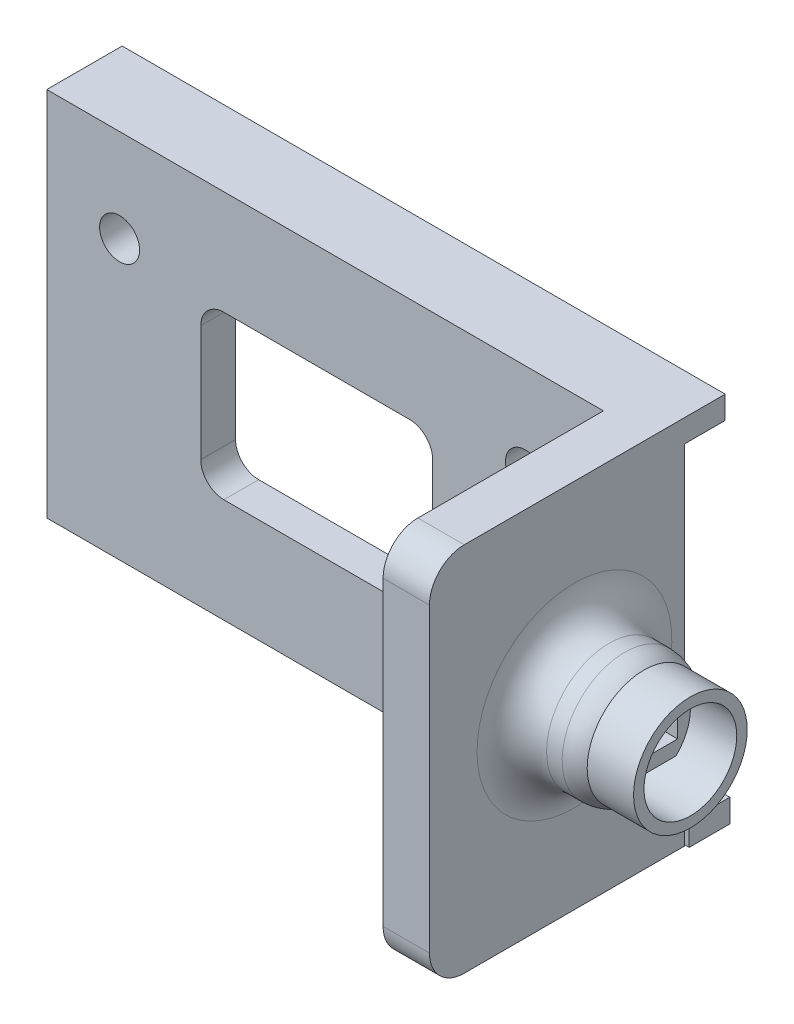
SolidWorks part; units mm, degrees
ref_plane "Front Plane" through (0, 0, 0) normal (0, 0, 1) x (1, 0, 0)
ref_plane "Top Plane" through (0, 0, 0) normal (0, 1, 0) x (1, 0, 0)
ref_plane "Right Plane" through (0, 0, 0) normal (1, 0, 0) x (0, 0, -1)
sketch "Sketch1" plane through (0, 0, 0) normal (0, 0, 1) x (1, 0, 0)
  line L1 (0, 0) -> (52, 0)
  line L2 (0, 0) -> (0, -32)
  line L3 (0, -32) -> (52, -32)
  line L4 (52, 0) -> (52, -32)
  dimension "D1" = 52
  dimension "D2" = 32
extrude "Boss-Extrude1" add sketch "Sketch1" along normal blind 3
ref_plane "Plane1" through (0, 0, 2) normal (0, 0, -1) x (-1, 0, 0)
sketch "Sketch2" plane through (0, 0, 2) normal (0, 0, -1) x (-1, 0, 0)
  line L1 (-48, 0) -> (-52, 0)
  line L2 (-48, 0) -> (-48, -32)
  line L3 (-48, -32) -> (-52, -32)
  line L4 (-52, 0) -> (-52, -32)
  dimension "D1" = 4
extrude "Boss-Extrude2" add sketch "Sketch2" against normal blind 20
fillet "Fillet1" radius 3 2 edges at (50, -32, 22) (50, 0, 22)
sketch "Sketch4" plane through (0, 0, 3) normal (0, 0, 1) x (1, 0, 0)
  line L0 (48, 0) -> (0, 0) construction
  circle A0 centre (41.2777, -8) radius 1.725
  circle A1 centre (6.2777, -8) radius 1.725
  dimension "D1" = 35
  dimension "D2" = 8
  dimension "D3" = 8
extrude "Cut-Extrude2" cut sketch "Sketch4" against normal up to surface (3 mm away) up to face at (26, -16, 0)
sketch "Sketch5" plane through (0, 0, 0) normal (0, 0, -1) x (-1, 0, 0)
  line L6 (0, 0) -> (0, -32) construction
  line L7 (-52.3955, -31.9041) -> (0, -31.9041)
  line L8 (-52.3955, -31.9041) -> (-52.3955, -29.9041)
  line L9 (-52.3955, -29.9041) -> (0, -29.9041)
  line L10 (0, -31.9041) -> (0, -29.9041)
  line L12 (-52, -1.966) -> (0, -2.1935)
  line L13 (0, 0) -> (0, -2.1935)
  line L14 (-52, 0) -> (0, 0)
  line L15 (-52, 0) -> (-52, -1.966)
  dimension "D1" = 2
extrude "Boss-Extrude3" add sketch "Sketch5" along normal blind 3.5
sketch "Sketch6" plane through (0, 0, 3) normal (0, 0, 1) x (1, 0, 0)
  line L0 (48, 0) -> (0, 0) construction
  line L1 (33.2777, -9) -> (13.2777, -9)
  line L2 (33.2777, -9) -> (33.2777, -23)
  line L3 (33.2777, -23) -> (13.2777, -23)
  line L4 (13.2777, -9) -> (13.2777, -23)
  circle A0 centre (6.2777, -8) radius 1.725 construction
  dimension "D3" = 7
  dimension "D1" = 14
  dimension "D2" = 20
  dimension "D4" = 9
extrude "Cut-Extrude3" cut sketch "Sketch6" against normal up to surface (3 mm away) up to face at (43.0027, -8, 0)
sketch "Sketch7" plane through (52, 0, 0) normal (1, 0, 0) x (0, 0, -1)
  line L0 (-22, -16) -> (2.0181, -16) construction
  line L1 (-12.4, -17.7) -> (-6.6, -17.7)
  line L2 (-12.4, -17.7) -> (-12.4, -14.3)
  line L3 (-12.4, -14.3) -> (-6.6, -14.3)
  line L4 (-6.6, -17.7) -> (-6.6, -14.3)
  line L5 (-22, -3) -> (-22, -29) construction
  line L6 (-9.5, -32) -> (-9.5, 5.4647) construction
  line L7 (-19, -32) -> (0, -32) construction
  line L8 (-13.6, -13.1) -> (-5.4, -13.1)
  line L9 (-5.4, -18.9) -> (-5.4, -13.1)
  line L10 (-13.6, -18.9) -> (-5.4, -18.9)
  line L11 (-13.6, -18.9) -> (-13.6, -13.1)
  dimension "D5" = 1.2
  dimension "D1" = 5.8
  dimension "D2" = 3.4
  dimension "D3" = 1.7
  dimension "D4" = 2.9
sketch "Sketch8" plane through (52, 0, 0) normal (1, 0, 0) x (0, 0, -1)
  line L0 (-9.5, -16) -> (-9.5, 10.2333) construction
  line L1 (-22, -16) -> (3, -16) construction
  line L3 (0, -29.9041) -> (0, -1.966) construction
  line L6 (-19, -32) -> (0, -32) construction
  circle A0 centre (-9.5, -16) radius 4.25
  circle A1 centre (-9.5, -16) radius 5.4
  point P6 (0, 0)
  point P10 (0, 0)
  point P12 (-9.9627, -32)
  dimension "D1" = 10.8
  dimension "D2" = 8.5
  dimension "D3" = 9.5
  dimension "D4" = 16
extrude "Boss-Extrude4" add sketch "Sketch7" along normal blind 6
sketch "Sketch10" plane through (52, 0, 0) normal (1, 0, 0) x (0, 0, -1)
  line L0 (-19, -32) -> (0, -32) construction
  line L1 (0, -29.9041) -> (0, -1.966) construction
  circle A0 centre (-9.5, -16) radius 4
  circle A1 centre (-9.5, -16) radius 4.9
  dimension "D1" = 9.8
  dimension "D2" = 8
  dimension "D3" = 16
  dimension "D4" = 9.5
extrude "Boss-Extrude6" add sketch "Sketch10" along normal blind 10
extrude "Boss-Extrude5" add sketch "Sketch8" along normal blind 6
fillet "Fillet2" radius 2 4 edges at (13.2777, -9, 1.5) (13.2777, -23, 1.5) (33.2777, -9, 1.5) (33.2777, -23, 1.5)
fillet "Fillet3" radius 3 2 edges at (52, -21.4, 9.5) (58, -16, 4.1)
